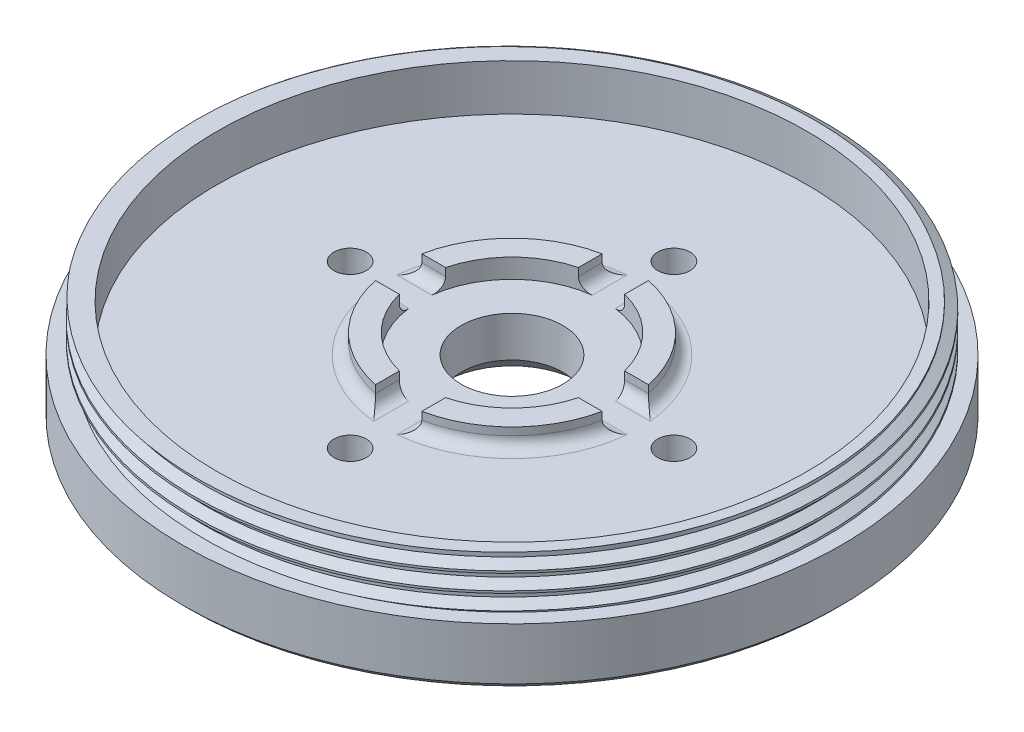
SolidWorks part; units mm, degrees
ref_plane "Front plane" through (0, 0, 0) normal (0, 0, 1) x (1, 0, 0)
ref_plane "Top plane" through (0, 0, 0) normal (0, 1, 0) x (1, 0, 0)
ref_plane "Right plane" through (0, 0, 0) normal (1, 0, 0) x (0, 0, -1)
ref_axis "Axis X" through (0, 0, 0) along (1, 0, 0)
ref_axis "Axis Y" through (0, 0, 0) along (0, 1, 0)
ref_axis "Axis Z" through (0, 0, 0) along (0, 0, 1)
sketch "Sketch1" plane through (0, 0, 0) normal (0, 1, 0) x (1, 0, 0)
  circle A0 centre (0, 0) radius 28.5
  circle A1 centre (0, 0) radius 4.4
  circle A2 centre (0, 0) radius 14 construction
  circle A3 centre (0, 14) radius 1.4
  circle A4 centre (14, 0) radius 1.4
  circle A5 centre (0, -14) radius 1.4
  circle A6 centre (-14, 0) radius 1.4
  point P16 (0, 0)
  dimension "D1" = 57
  dimension "D2" = 8.8
  dimension "D3" = 28
  dimension "D4" = 2.8
  dimension "D5" = 4
extrude "Extrude1" add sketch "Sketch1" along normal blind 5
sketch "Sketch8" plane through (0, 5, 0) normal (0, 1, 0) x (1, 0, 0)
  circle A1 centre (0, 0) radius 25.5
  circle A3 centre (0, 0) radius 26.45
  dimension "D1" = 51
  dimension "D2" = 0.95
extrude "Бобышка-Вытянуть1" add sketch "Sketch8" along normal blind 4
thread "Резьба1" pitch 1.5 method extrude trim with start face yes trim with end face yes profile "Профиль резьбы1" start angle 0, offset 2, length 0, pitch 1.5, diameter 52.9
ref_plane "Плоскость1" through (-26.45, 11, 0) normal (0, 0, 1) x (-1, 0, 0)
sketch "Профиль резьбы1" plane through (-26.45, 11, 0) normal (0, 0, 1) x (-1, 0, 0)
  line L0 (0, 0) -> (0, 1.5) construction
  line L1 (0, 0) -> (0.8119, 0.4687)
  line L2 (0.8119, 0.4687) -> (0.8119, 0.6562)
  line L3 (0.8119, 0.6562) -> (0, 1.125)
  line L4 (0.8119, 0.5625) -> (0, 0.5625) construction
  line L11 (0, 0) -> (0, 1.125)
  point P2 (0, 0)
  dimension "Pitch" = 1.5
  dimension "Profile_Angle" = 60
  dimension "Profile_Land" = 0.1875
  dimension "Profile_Height" = 0.8119
sketch "Эскиз3" plane through (0, 5, 0) normal (0, 1, 0) x (1, 0, 0)
  line L0 (0, 0) -> (0, 10) construction
  line L1 (-2, 9.798) -> (-2, 7.746)
  line L2 (2, 9.798) -> (2, 7.746)
  line L3 (9.798, 2) -> (7.746, 2)
  line L4 (9.798, -2) -> (7.746, -2)
  line L5 (2, -9.798) -> (2, -7.746)
  line L6 (-2, -9.798) -> (-2, -7.746)
  line L7 (-9.798, -2) -> (-7.746, -2)
  line L8 (-9.798, 2) -> (-7.746, 2)
  arc A0 (-2, 7.746) -> (-7.746, 2) centre (0, 0) ccw
  arc A1 (-2, 9.798) -> (-9.798, 2) centre (0, 0) ccw
  arc A2 (7.746, 2) -> (2, 7.746) centre (0, 0) ccw
  arc A3 (9.798, 2) -> (2, 9.798) centre (0, 0) ccw
  arc A4 (-7.746, -2) -> (-2, -7.746) centre (0, 0) ccw
  arc A5 (-9.798, -2) -> (-2, -9.798) centre (0, 0) ccw
  arc A6 (2, -7.746) -> (7.746, -2) centre (0, 0) ccw
  arc A7 (2, -9.798) -> (9.798, -2) centre (0, 0) ccw
  dimension "D1" = 16
  dimension "D2" = 2
  dimension "D3" = 4
  dimension "D4" = 4
extrude "Бобышка-Вытянуть2" add sketch "Эскиз3" along normal blind 1.6667
fillet "Скругление1" radius 1 12 edges at (-2, 5, -8.772) (2, 5, -8.772) (7.0711, 5, -7.0711) (8.772, 5, -2) (8.772, 5, 2) (7.0711, 5, 7.0711) (-7.0711, 5, -7.0711) (-7.0711, 5, 7.0711) (2, 5, 8.772) (-2, 5, 8.772) (-8.772, 5, 2) (-8.772, 5, -2)
chamfer "Chamfer2" distance 1.5 angle 45 1 edges at (0, 0, 4.4)
chamfer "Chamfer3" distance 0.5 angle 45 1 edges at (0, 0, 28.5)
chamfer "Chamfer4" distance 1 angle 45 4 edges at (0, 0, -12.6) (14, 0, 1.4) (-14, 0, 1.4) (0, 0, 15.4)
equation "\"motor_D\"= 49'Motor diameter"
equation "\"motor_H\"= 19'Motor heigh"
equation "\"motor_d1\"= 38.5'Seating diameter of screws on the fixed part of the motor"
equation "\"motor_s1\"= 2.5'Screws diameter on the fixed part of motor"
equation "\"motor_a2\"= 0'Seating parameter in rectangle of screws on the moving part of the motor"
equation "\"motor_s2\"= 3'Screws diameter on the moving part of motor"
equation "\"motor_Dc\"= 5'Central hole diameter of motor"
equation "\"bearing_d1\"= 8'Bearing inner diameter"
equation "\"bearing_d2\"= 16'Bearing external diameter"
equation "\"bearing h\"= 5'Bearing heigh"
equation "\"pin_d\"= 2'Pin diameter"
equation "\"pin_h\"= 13'Pin heigh"
equation "\"magnet_d1\"= 5'Magnet inner diameter"
equation "\"magnet_d2\"= 9.5'Magnet external diameter"
equation "\"magnet_h\"= 3'Magnet heigh"
equation "\"motor_b2\"= 0'Seating parameter in rectangle of screws on the moving part of the motor"
equation "\"motor_d2\"= 25'Seating diameter of screws on the moving part of the motor (if this parameter is not determine, write 0)"
equation "\"motor_cmd\"= 17'Central magnet mount diameter"
equation "\"motor_cmh\"= 1'Central magnet mount heigh (if not write 0)"
equation "\"motor_whR\"= 17'Distance from center of motor to wires"
equation "\"D1@Sketch1\"= IIF ( \"motor_D\" < 34 , 41 , \"motor_D\" + 8 )"
equation "\"D2@Sketch1\"=\"ft_sensor_d1\"-1"
equation "\"D4@Sketch1\"=3-\"print_offset\""
equation "\"print_offset\"= 0.2'Offset for printing holes"
equation "\"ft_sensor_d1\"= 9.8"
equation "\"ft_sensor_d2\"= 24.9"
equation "\"ft_sensor_d3\"= 22.6'Inner diameter of "
equation "\"ft_sensor_h\"= 7.1"
equation "\"ft_sensor_whD\" = 5"
equation "\"D1@Sketch8\" = IIF ( \"motor_D\" < 34 , 41 , \"motor_D\" + 8 ) - 6"
equation "\"D2@Sketch8\"= 0.95"
equation "\"D1@Эскиз3\"=\"bearing_d2\""
equation "\"D1@Бобышка-Вытянуть2\"=\"bearing h\"/3"
